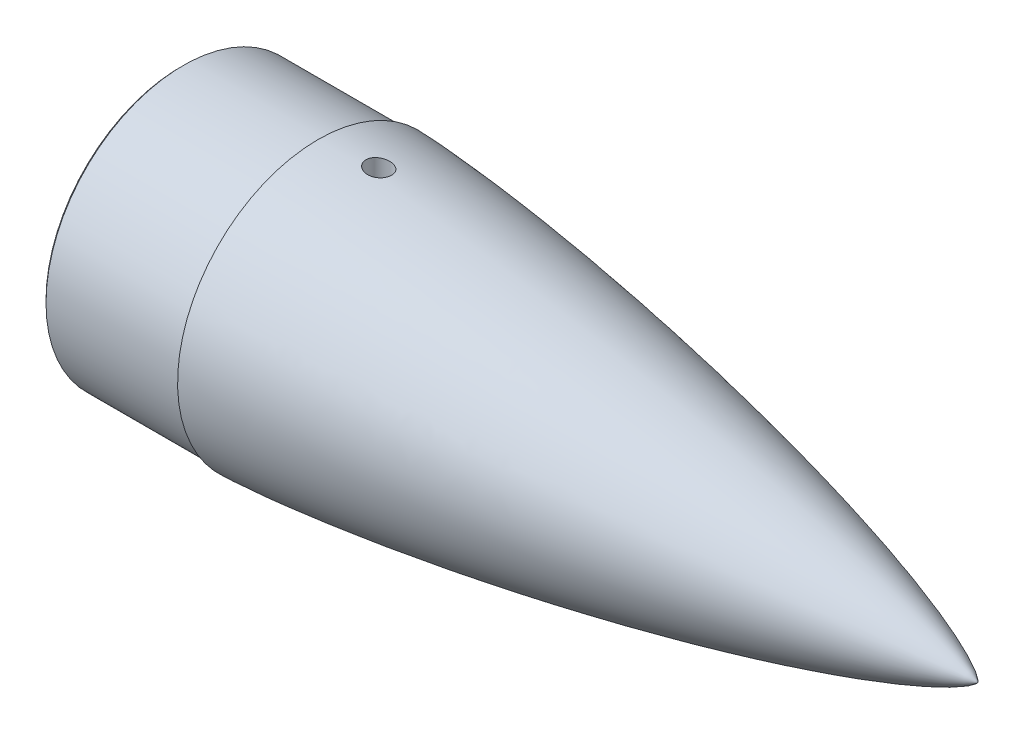
SolidWorks part; units mm, degrees
material "Plain Carbon Steel"
ref_plane "Front Plane" through (0, 0, 0) normal (0, 0, 1) x (1, 0, 0)
ref_plane "Top Plane" through (0, 0, 0) normal (0, 1, 0) x (1, 0, 0)
ref_plane "Right Plane" through (0, 0, 0) normal (1, 0, 0) x (0, 0, -1)
ref_axis "Axis1" through (46.9179, 0, 0) along (-1, 0, 0)
sketch "Sketch10" plane through (0, 0, 0) normal (0, 0, 1) x (1, 0, 0)
  line L1 (-1.0327, 0) -> (486.9547, 0) construction
  line L2 (11.1125, 81.9998) -> (11.1125, 67.4998)
  line L3 (11.1125, 81.9998) -> (-84.6045, 81.9998)
  line L4 (408.9673, 0) -> (368.9673, 0)
  line L5 (-84.6045, 81.9998) -> (-84.6045, 84.9998)
  line L6 (-84.6045, 84.9998) -> (0.3953, 84.9998)
  line L7 (0.3953, 84.9998) -> (0.3953, 86.9998)
  line L8 (11.1125, 67.4998) -> (129.3045, 67.4998)
  line L9 (46.9179, 0) -> (-46.1272, 0) construction
  spline S0 degree 4 poles (408.9673, 0) (408.9649, 0.0135) (408.958, 0.0399) (408.9365, 0.0905) (408.8922, 0.1741) (408.8263, 0.2756) (408.7217, 0.4158) (408.5611, 0.6051) (408.3056, 0.8724) (407.8697, 1.2753) (407.121, 1.8851) (405.8038, 2.8259) (403.4624, 4.2872) (399.3253, 6.5318) (392.4811, 9.7589) (380.6621, 14.628) (363.6372, 20.7117) (342.2152, 27.4765) (317.4285, 34.4976) (291.8793, 41.1048) (266.2105, 47.229) (240.4455, 52.9334) (214.5989, 58.2554) (188.6809, 63.2176) (165.9462, 67.2533) (146.422, 70.4938) (130.1279, 73.0449) (117.0786, 74.9942) (104.0155, 76.8485) (92.5733, 78.3845) (82.7571, 79.6356) (74.5713, 80.6322) (68.0193, 81.4008) (61.4637, 82.1394) (54.9047, 82.8464) (48.3422, 83.5199) (41.7761, 84.1578) (36.0275, 84.6822) (31.0979, 85.1052) (26.9883, 85.4387) (23.6997, 85.6932) (20.0858, 85.9584) (16.7199, 86.189) (13.6021, 86.387) (10.7327, 86.5546) (8.4366, 86.6787) (6.14, 86.7922) (4.1299, 86.8793) (2.4065, 86.9446) (1.2573, 86.979) (0.6827, 86.9949) (0.3953, 86.9998) knots 0 0 0 0 0 0.00013 0.00026 0.00052 0.0009 0.00128 0.001925 0.002882 0.004418 0.006927 0.011111 0.018279 0.030673 0.051704 0.083102 0.139909 0.202703 0.265496 0.32829 0.391083 0.453877 0.516671 0.579464 0.642258 0.673655 0.705051 0.736448 0.767845 0.799242 0.81494 0.830639 0.846337 0.862036 0.877734 0.893432 0.909131 0.924829 0.932678 0.940527 0.948377 0.956226 0.967169 0.972641 0.978113 0.983585 0.989056 0.994528 0.997264 1 1 1 1 1 construction
  spline S1 degree 4 poles (408.9673, 0) (408.9649, 0.0135) (408.958, 0.0399) (408.9365, 0.0905) (408.8922, 0.1741) (408.8263, 0.2756) (408.7217, 0.4158) (408.5611, 0.6051) (408.3056, 0.8724) (407.8697, 1.2753) (407.121, 1.8851) (405.8038, 2.8259) (403.4624, 4.2872) (399.3253, 6.5318) (392.4811, 9.7589) (380.6621, 14.628) (363.6372, 20.7117) (342.2152, 27.4765) (317.4285, 34.4976) (291.8793, 41.1048) (266.2105, 47.229) (240.4455, 52.9334) (214.5989, 58.2554) (188.6809, 63.2176) (165.9462, 67.2533) (146.422, 70.4938) (130.1279, 73.0449) (117.0786, 74.9942) (104.0155, 76.8485) (92.5733, 78.3845) (82.7571, 79.6356) (74.5713, 80.6322) (68.0193, 81.4008) (61.4637, 82.1394) (54.9047, 82.8464) (48.3422, 83.5199) (41.7761, 84.1578) (36.0275, 84.6822) (31.0979, 85.1052) (26.9883, 85.4387) (23.6997, 85.6932) (20.0858, 85.9584) (16.7199, 86.189) (13.6021, 86.387) (10.7327, 86.5546) (8.4366, 86.6787) (6.14, 86.7922) (4.1299, 86.8793) (2.4065, 86.9446) (1.2573, 86.979) (0.6827, 86.9949) (0.3953, 86.9998) knots 0 0 0 0 0 0.00013 0.00026 0.00052 0.0009 0.00128 0.001925 0.002882 0.004418 0.006927 0.011111 0.018279 0.030673 0.051704 0.083102 0.139909 0.202703 0.265496 0.32829 0.391083 0.453877 0.516671 0.579464 0.642258 0.673655 0.705051 0.736448 0.767845 0.799242 0.81494 0.830639 0.846337 0.862036 0.877734 0.893432 0.909131 0.924829 0.932678 0.940527 0.948377 0.956226 0.967169 0.972641 0.978113 0.983585 0.989056 0.994528 0.997264 1 1 1 1 1
  spline S2 degree 4 poles (368.9673, 0) (368.9653, 0.0123) (368.9594, 0.0365) (368.9406, 0.083) (368.9023, 0.1587) (368.8455, 0.2503) (368.7557, 0.3766) (368.6167, 0.5484) (368.3929, 0.7936) (368.0087, 1.1649) (367.3447, 1.7299) (366.1761, 2.6016) (364.0928, 3.96) (360.426, 6.0407) (354.4022, 9.0183) (344.043, 13.5077) (329.152, 19.1285) (310.4252, 25.3986) (288.7413, 31.9337) (266.3785, 38.1061) (243.9014, 43.8469) (221.332, 49.212) (198.684, 54.2345) (175.9669, 58.9343) (156.0346, 62.7717) (138.9133, 65.8645) (124.6221, 68.3077) (113.1754, 70.1797) (101.7151, 71.9664) (91.6754, 73.4517) (83.0615, 74.6659) (75.8775, 75.6363) (70.1269, 76.3867) (64.3728, 77.1101) (58.6152, 77.8049) (52.854, 78.4695) (47.0892, 79.1019) (42.0417, 79.6247) (37.7129, 80.0488) (34.1039, 80.385) (31.2157, 80.6428) (28.0648, 80.911) (24.6507, 81.1843) (21.4654, 81.4195) (18.5093, 81.6177) (16.0448, 81.767) (14.3191, 81.8612) (12.8395, 81.9336) (11.8527, 81.9739) (11.3593, 81.993) (11.1125, 81.9998) knots 0 0 0 0 0 0.000135 0.00027 0.00054 0.00092 0.001299 0.001947 0.002931 0.004512 0.007081 0.01138 0.018708 0.031424 0.052705 0.084103 0.14091 0.203703 0.266497 0.329291 0.392084 0.454878 0.517672 0.580465 0.643259 0.674656 0.706052 0.737449 0.768846 0.800243 0.815941 0.831639 0.847338 0.863036 0.878735 0.894433 0.910132 0.92583 0.933679 0.941528 0.949378 0.957227 0.96792 0.978613 0.98396 0.989307 0.994653 0.997327 1 1 1 1 1 construction
  spline S3 degree 4 poles (368.9673, 0) (368.9653, 0.0123) (368.9594, 0.0365) (368.9406, 0.083) (368.9023, 0.1587) (368.8455, 0.2503) (368.7557, 0.3766) (368.6167, 0.5484) (368.3929, 0.7936) (368.0087, 1.1649) (367.3447, 1.7299) (366.1761, 2.6016) (364.0928, 3.96) (360.426, 6.0407) (354.4022, 9.0183) (344.043, 13.5077) (329.152, 19.1285) (310.4252, 25.3986) (288.7413, 31.9337) (266.3785, 38.1061) (243.9014, 43.8469) (221.332, 49.212) (198.684, 54.2345) (175.9669, 58.9343) (156.0346, 62.7717) (141.5091, 65.3956) (132.6794, 66.9245) (129.5628, 67.4559) (129.3045, 67.4998) knots 0 0 0 0 0 0.000135 0.00027 0.00054 0.00092 0.001299 0.001947 0.002931 0.004512 0.007081 0.01138 0.018708 0.031424 0.052705 0.084103 0.14091 0.203703 0.266497 0.329291 0.392084 0.454878 0.517672 0.580465 0.643259 0.674656 0.677492 0.677492 0.677492 0.677492 0.677492
  dimension "D1" = 86.9998
  dimension "D2" = 3
  dimension "D3" = 410
  dimension "D4" = 84.9998
  dimension "D5" = 370
  dimension "D6" = 84.9998
  dimension "D7" = 19.5
  dimension "D8" = 118.192
revolve "Revolve1" add sketch "Sketch10" angle 360 about axis through (46.9179, 0, 0) along (-1, 0, 0)
chamfer "Chamfer1" distance 1.5 angle 45 1 edges at (-84.6045, 0, -84.9998)
ref_plane "Plane2" through (11.1125, 0, 0) normal (-1, 0, 0) x (0, 0, 1)
sketch "Sketch12" plane through (11.1125, 0, 0) normal (-1, 0, 0) x (0, 0, 1)
  line L0 (-81.9998, 0) -> (-67.4998, 0)
  circle A2 centre (0, 0) radius 81.9998 construction
  circle A3 centre (0, 0) radius 67.4998 construction
  circle A4 centre (-74.7498, 0) radius 4
  circle A5 centre (-37.3749, 64.7353) radius 4
  circle A6 centre (37.3749, 64.7353) radius 4
  circle A7 centre (74.7498, 0) radius 4
  circle A8 centre (37.3749, -64.7353) radius 4
  circle A9 centre (-37.3749, -64.7353) radius 4
  point P17 (-50.2998, -44.6412)
  point P25 (0, 0)
  dimension "D1" = 6
hole_wizard "Tapped Hole for M4x0.7 Helicoil1" positions "Sketch17" profile "Sketch18" tap size "M4x0.7" standard "Helicoil® Metric"
sketch "Sketch17" plane through (11.1125, 0, 0) normal (-1, 0, 0) x (0, 0, 1)
  point P0 (-37.3749, 64.7353)
sketch "Sketch18" plane through (11.1125, 64.7353, -37.3749) normal (0, 1, 0) x (0, 0, 1)
  line L0 (0, 0) -> (0, 31.2618)
  line L1 (0, 31.2618) -> (2.1, 30)
  line L2 (2.1, 30) -> (2.1, 0)
  line L5 (2.1, 0) -> (0, 0)
  line L10 (0, 31.2618) -> (-2.1, 30) construction
  line L11 (0, -6.35) -> (0, 107.95) construction
  dimension "Tap Drill Dia." = 4.2
  dimension "Tap Drill Depth" = 30
  dimension "Drill Angle" = 118
cosmetic thread "Hole Thread3" parameters "D1"=4.7, "D2"=5.007
pattern_circular "CirPattern1" count 6 over 360 about axis through (11.1125, 0, 0) along (1, 0, 0) of "Tapped Hole for M4x0.7 Helicoil1"
ref_plane "Plane3" through (0, 60, 0) normal (0, 1, 0) x (1, 0, 0)
sketch "Sketch20" plane through (0, 60, 0) normal (0, 1, 0) x (1, 0, 0)
  line L0 (46.9179, 0) -> (-46.1272, 0) construction
  line L1 (24.7702, 25) -> (64.7702, 25)
  line L2 (24.7702, 25) -> (24.7702, -15)
  line L3 (24.7702, -15) -> (64.7702, -15)
  line L4 (64.7702, 25) -> (64.7702, -15)
  line L5 (24.7702, 25) -> (64.7702, -15) construction
  line L6 (24.7702, -15) -> (64.7702, 25) construction
  point P4 (44.7702, 5)
  dimension "D1" = 40
  dimension "D2" = 15
  dimension "D3" = 40
extrude "Cut-Extrude3" cut sketch "Sketch20" along normal blind 12
sketch "Sketch22" plane through (0, 60, 0) normal (0, 1, 0) x (1, 0, 0)
  circle A0 centre (32, 6) radius 7.5
  dimension "D1" = 15
extrude "Cut-Extrude4" cut sketch "Sketch22" along normal through all
equation "\"TubeDiameter\" = 6.250in"
